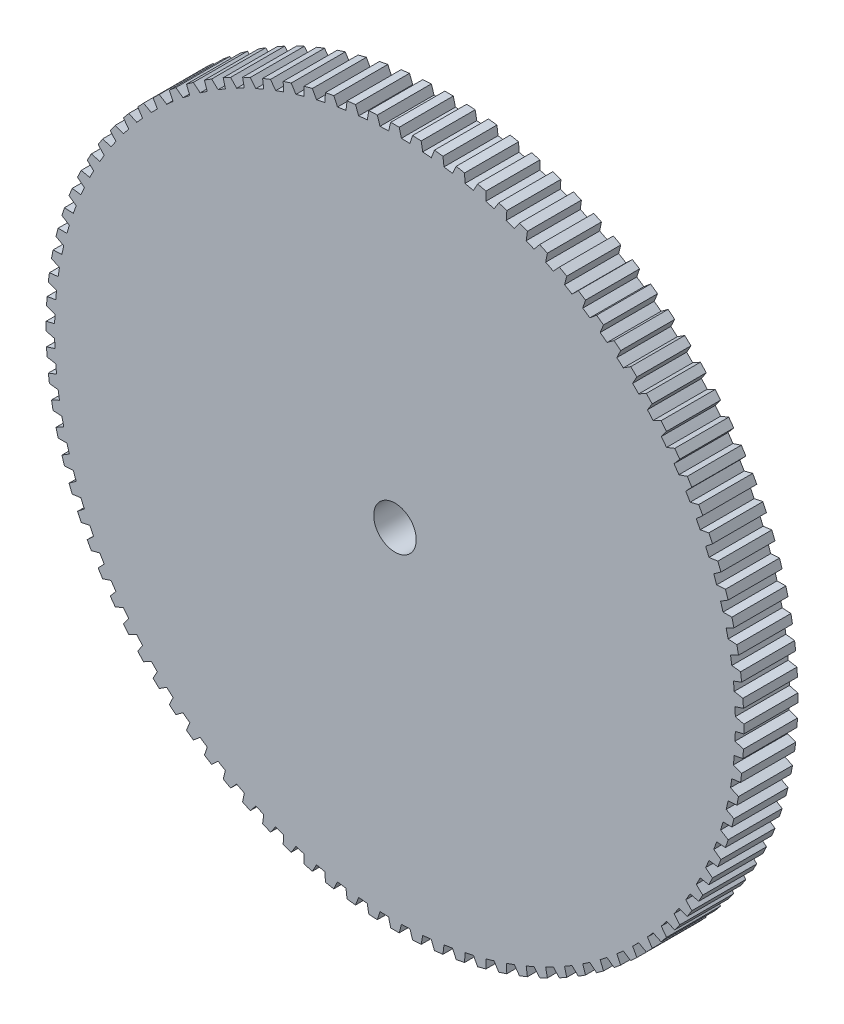
SolidWorks part; units mm, degrees
ref_plane "Front Plane" through (0, 0, 0) normal (0, 0, 1) x (1, 0, 0)
ref_plane "Top Plane" through (0, 0, 0) normal (0, 1, 0) x (1, 0, 0)
ref_plane "Right Plane" through (0, 0, 0) normal (1, 0, 0) x (0, 0, -1)
sketch "Sketch1" plane through (0, 0, 0) normal (0, 0, 1) x (1, 0, 0)
  circle A0 centre (0, 0) radius 40
  circle A1 centre (0, 0) radius 2.5
  dimension "D1" = 80
  dimension "D2" = 5
extrude "Boss-Extrude1" add sketch "Sketch1" along normal blind 6.35
sketch "Sketch2" plane through (0, 0, 6.35) normal (0, 0, 1) x (1, 0, 0)
  line L0 (0, -1000) -> (0, 49000) construction
  line L1 (-0.5, 41) -> (0.5, 41)
  line L2 (0.5, 41) -> (1, 39)
  line L3 (1, 39) -> (-1, 39)
  line L4 (-1, 39) -> (-0.5, 41)
  circle A0 centre (0, 0) radius 40 construction
  point P5 (0, 41)
  point P8 (0, 39)
  dimension "D1" = 2
  dimension "D2" = 1
  dimension "D3" = 39
  dimension "D4" = 41
extrude "Boss-Extrude2" add sketch "Sketch2" against normal blind 6.35
pattern_circular "CirPattern1" count 100 over 360 about axis through (0, 0, 6.35) along (0, 0, -1) of "Boss-Extrude2"
